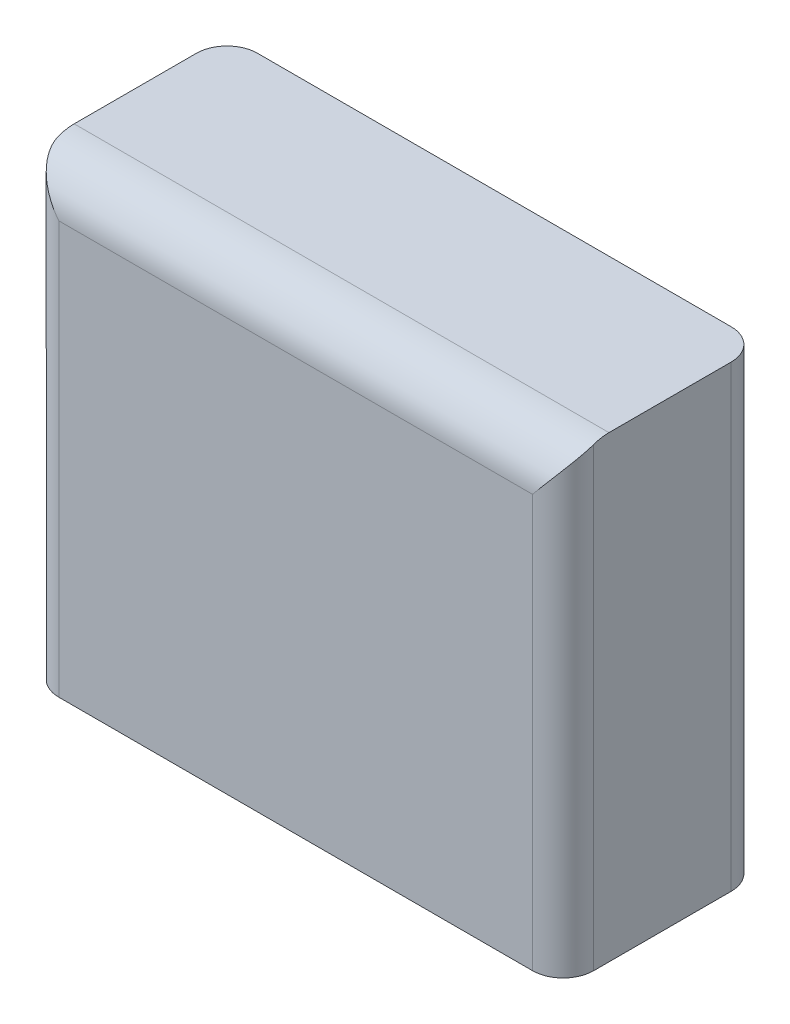
SolidWorks part; units mm, degrees
material "K110"
ref_plane "Front Plane" through (0, 0, 0) normal (0, 0, 1) x (1, 0, 0)
ref_plane "Top Plane" through (0, 0, 0) normal (0, 1, 0) x (1, 0, 0)
ref_plane "Right Plane" through (0, 0, 0) normal (1, 0, 0) x (0, 0, -1)
sketch "Sketch1" plane through (0, 0, 0) normal (0, 1, 0) x (1, 0, 0)
  line L1 (-17.5, -6.5) -> (17.5, -6.5)
  line L2 (-17.5, -6.5) -> (-17.5, 6.5)
  line L3 (-17.5, 6.5) -> (17.5, 6.5)
  line L4 (17.5, -6.5) -> (17.5, 6.5)
  line L5 (-17.5, -6.5) -> (17.5, 6.5) construction
  line L6 (-17.5, 6.5) -> (17.5, -6.5) construction
  point P0 (0, 0)
  dimension "D1" = 13
  dimension "D2" = 35
extrude "Boss-Extrude1" add sketch "Sketch1" against normal blind 30
fillet "Fillet1" radius 2 4 edges at (-17.5, -15, -6.5) (-17.5, -15, 6.5) (17.5, -15, -6.5) (17.5, -15, 6.5)
fillet "Fillet2" radius 3 1 edges at (0, 0, 6.5) tangent propagation no
hole_wizard "M6 Tapped Hole1" positions "Sketch4" profile "Sketch3" tap size "M6" standard "ISO"
sketch "Sketch4" plane through (0, -30, 0) normal (0, -1, 0) x (-1, 0, 0)
  line L0 (-17.5, -4.5) -> (-17.5, 4.5) construction
  line L1 (17.5, 4.5) -> (17.5, -4.5) construction
  point P0 (-10, 0)
  point P2 (10, 0)
  dimension "D1" = 7.5
  dimension "D2" = 7.5
sketch "Sketch3" plane through (10, -30, 0) normal (1, 0, 0) x (0, 0, -1)
  line L0 (0, 0) -> (0, 18.5022)
  line L1 (0, 18.5022) -> (2.5, 17)
  line L2 (2.5, 17) -> (2.5, 0.525)
  line L3 (2.5, 0.525) -> (3.025, 0)
  line L5 (3.025, 0) -> (0, 0)
  line L6 (-2.5, 0.525) -> (-3.025, 0) construction
  line L10 (0, 18.5022) -> (-2.5, 17) construction
  line L11 (0, -6.35) -> (0, 107.95) construction
  dimension "Tap Drill Dia." = 5
  dimension "Tap Drill Depth" = 17
  dimension "Near C'Sink Dia." = 6.05
  dimension "Near C'Sink Angle" = 90
  dimension "Drill Angle" = 118
cosmetic thread "Hole Thread1"
cosmetic thread "Hole Thread2"
